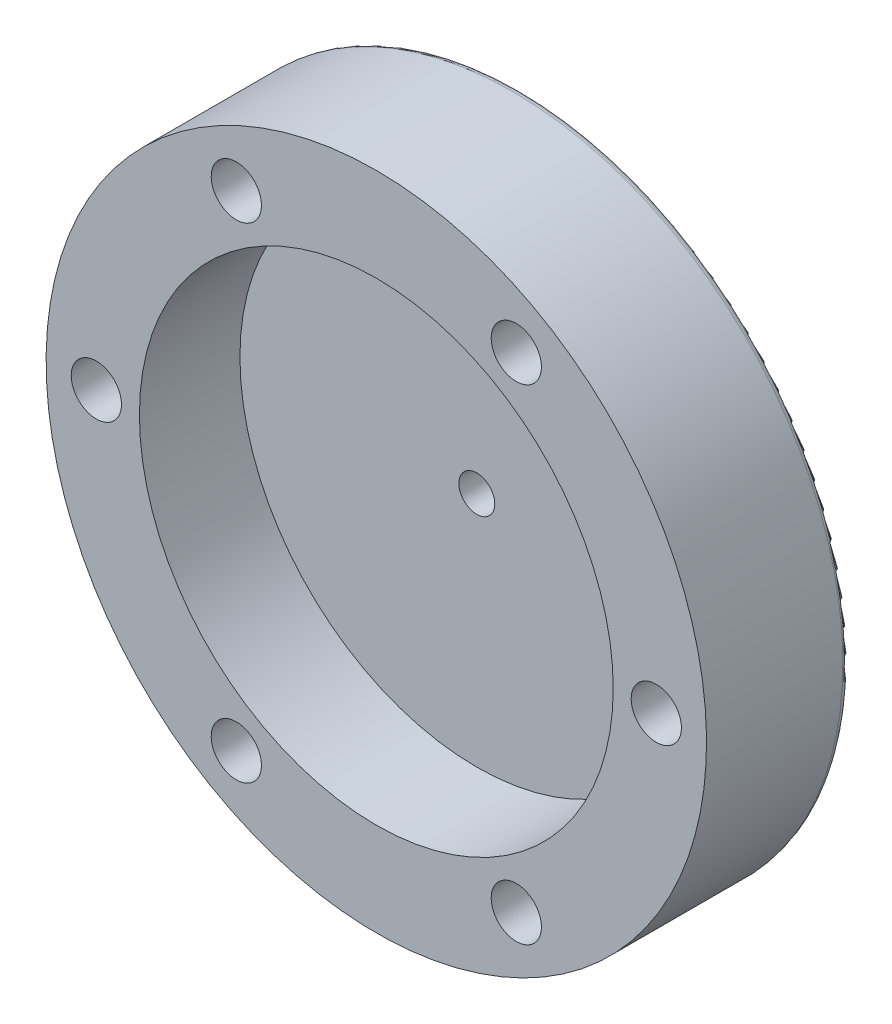
SolidWorks part; units mm, degrees
ref_plane "Front Plane" through (0, 0, 0) normal (0, 0, 1) x (1, 0, 0)
ref_plane "Top Plane" through (0, 0, 0) normal (0, 1, 0) x (1, 0, 0)
ref_plane "Right Plane" through (0, 0, 0) normal (1, 0, 0) x (0, 0, -1)
sketch "Sketch1" plane through (0, 0, 0) normal (1, 0, 0) x (0, 0, -1)
  line L0 (0, 33) -> (-14, 33)
  line L1 (-14, 33) -> (-14, 46)
  line L2 (-14, 46) -> (6, 46)
  line L3 (6, 46) -> (6, 12)
  line L4 (6, 12) -> (16, 12)
  line L5 (16, 12) -> (16, 0)
  line L6 (16, 0) -> (0, 0)
  line L7 (0, 0) -> (0, 33)
  dimension "D1" = 46
  dimension "D2" = 33
  dimension "D3" = 6
  dimension "D4" = 30
  dimension "D5" = 10
  dimension "D6" = 12
revolve "Revolve1" add sketch "Sketch1" angle 360 about L6
sketch "Sketch2" plane through (0, 0, -6) normal (0, 0, -1) x (-1, 0, 0)
  line L0 (0, 39) -> (0, 0) construction
  line L1 (0, 0) -> (19.5, -33.775) construction
  circle A0 centre (0, 0) radius 39 construction
  circle A1 centre (19.5, -33.775) radius 3.5
  circle A2 centre (-19.5, -33.775) radius 3.5
  circle A3 centre (-39, 0) radius 3.5
  circle A4 centre (-19.5, 33.775) radius 3.5
  circle A5 centre (19.5, 33.775) radius 3.5
  circle A6 centre (39, 0) radius 3.5
  point P18 (0, 0)
  dimension "D1" = 78
  dimension "D3" = 7
  dimension "D2" = 150
  dimension "D4" = 6
extrude "Cut-Extrude1" cut sketch "Sketch2" against normal through all
sketch "Sketch3" plane through (0, 0, -16) normal (0, 0, -1) x (-1, 0, 0)
  circle A0 centre (0, 0) radius 7
  circle A1 centre (0, 0) radius 2.5
  dimension "D1" = 14
  dimension "D2" = 5
extrude "Cut-Extrude2" cut sketch "Sketch3" against normal blind 10 contours A0
extrude "Cut-Extrude3" cut sketch "Sketch3<3>" against normal through all contours A1
sketch "Sketch3<3>" plane through (0, 0, -16) normal (0, 0, -1) x (-1, 0, 0) same geometry as "Sketch3"
fillet "Fillet1" radius 1 1 edges at (0, 46, -6)
